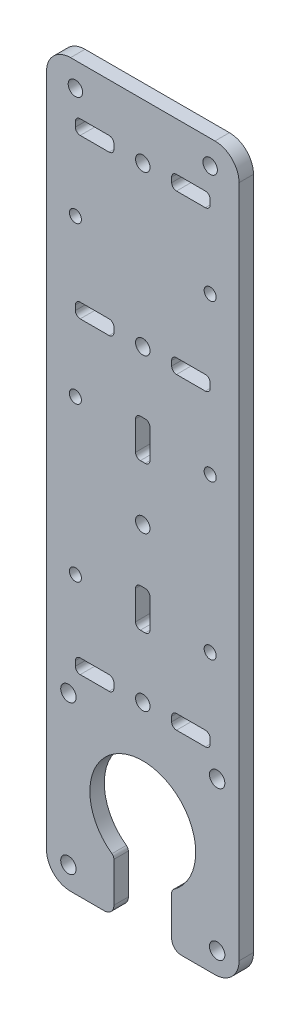
SolidWorks part; units mm, degrees
material "Acrylic (Medium-high impact)"
ref_plane "Front Plane" through (0, 0, 0) normal (0, 0, 1) x (1, 0, 0)
ref_plane "Top Plane" through (0, 0, 0) normal (0, 1, 0) x (1, 0, 0)
ref_plane "Right Plane" through (0, 0, 0) normal (1, 0, 0) x (0, 0, -1)
sketch "Sketch1" plane through (0, 0, 0) normal (0, 0, 1) x (1, 0, 0)
  line L0 (0, 75) -> (0, -75) construction
  line L1 (-20, 75) -> (20, 75)
  line L2 (-20, 75) -> (-20, -75)
  line L3 (-20, -75) -> (20, -75)
  line L4 (20, 75) -> (20, -75)
  line L5 (20, 0) -> (-20, 0) construction
  line L6 (0, -75) -> (0, -55) construction
  line L7 (0, -55) -> (6, -55) construction
  line L8 (6, -55) -> (6, -75) construction
  line L9 (0, -55) -> (-6, -55) construction
  line L10 (-6, -55) -> (-6, -75) construction
  line L11 (0, -55) -> (20, -75) construction
  line L12 (0, -55) -> (15.4503, -70.4503) construction
  line L13 (-6, -75) -> (-6, -64.2195)
  line L14 (6, -75) -> (6, -64.2195)
  line L15 (0, -75) -> (0, -35) construction
  line L16 (-20, -35) -> (20, -35) construction
  line L17 (0, -35) -> (0, -32) construction
  line L18 (-20, -32) -> (20, -32) construction
  circle A0 centre (0, -55) radius 11
  circle A1 centre (15.4503, -70.4503) radius 1.6
  circle A2 centre (-15.4503, -70.4503) radius 1.6
  circle A3 centre (-15.4503, -39.5497) radius 1.6
  circle A4 centre (15.4503, -39.5497) radius 1.6
  point P8 (0, 0)
  point P26 (0, -55)
  dimension "D1" = 4
extrude "Boss-Extrude1" add sketch "Sketch1" along normal blind 3 contours A0 L14 L3 L4 L1 L2 L13 A4 A3 A2 A1 region at (0, 5.617, 0)
fillet "Fillet1" radius 5 4 edges at (-20, -75, 1.5) (20, -75, 1.5) (-20, 75, 1.5) (20, 75, 1.5)
fillet "Fillet2" radius 2 2 edges at (6, -75, 1.5) (-6, -75, 1.5)
fillet "Fillet3" radius 1 2 edges at (6, -64.2195, 1.5) (-6, -64.2195, 1.5)
sketch "Sketch2" plane through (0, 0, 3) normal (0, 0, 1) x (1, 0, 0)
  line L0 (0, -75) -> (0, -35) construction
  line L1 (0, -35) -> (0, -33.5) construction
  line L2 (-20, -33.5) -> (20, -33.5) construction
  line L3 (-20, 70) -> (-20, -70) construction
  line L4 (20, 70) -> (20, -70) construction
  line L5 (-20, -35) -> (20, -35) construction
  line L6 (20, -35) -> (20, -32)
  line L7 (20, -32) -> (-20, -32) construction
  line L8 (-20, -32) -> (-20, -35)
  line L9 (0, 75) -> (0, 65) construction
  line L10 (-15, 75) -> (15, 75) construction
  line L11 (0, 65) -> (0, 62) construction
  line L12 (0, 62) -> (0, 32) construction
  line L13 (0, 32) -> (0, 29) construction
  line L14 (-20, 29) -> (20, 29) construction
  line L15 (20, 29) -> (20, 32) construction
  line L16 (20, 32) -> (-20, 32) construction
  line L17 (-20, 32) -> (-20, 29) construction
  line L18 (-20, 62) -> (20, 62) construction
  line L19 (20, 62) -> (20, 65) construction
  line L20 (-10, 65) -> (-10, -35) construction
  line L21 (-20, 65) -> (-20, 62) construction
  line L22 (-20, 65) -> (0, 65) construction
  line L23 (0, 65) -> (20, 65) construction
  line L24 (10, 65) -> (10, -35) construction
  line L25 (0, -33.5) -> (0, 30.5) construction
  line L26 (-10, 65) -> (-6, 65) construction
  line L27 (-10, 65) -> (-14, 65) construction
  line L28 (10, 65) -> (14, 65) construction
  line L29 (10, 65) -> (6, 65) construction
  line L30 (6, 65) -> (6, -35) construction
  line L31 (14, 65) -> (14, -35) construction
  line L32 (-14, 65) -> (-14, -35) construction
  line L33 (-6, 65) -> (-6, -35) construction
  line L34 (0, 29) -> (0, -32) construction
  line L35 (-14, 65) -> (-6, 65)
  line L36 (-14, 65) -> (-14, 62)
  line L37 (-14, 62) -> (-6, 62)
  line L38 (-6, 65) -> (-6, 62)
  line L39 (6, 65) -> (14, 65)
  line L40 (6, 65) -> (6, 62)
  line L41 (6, 62) -> (14, 62)
  line L42 (14, 65) -> (14, 62)
  line L43 (-14, 32) -> (-6, 32)
  line L44 (-14, 32) -> (-14, 29)
  line L45 (-14, 29) -> (-6, 29)
  line L46 (-6, 32) -> (-6, 29)
  line L47 (6, 32) -> (14, 32)
  line L48 (6, 32) -> (6, 29)
  line L49 (6, 29) -> (14, 29)
  line L50 (14, 32) -> (14, 29)
  line L51 (-14, -32) -> (-6, -32)
  line L52 (-14, -32) -> (-14, -35)
  line L53 (-14, -35) -> (-6, -35)
  line L54 (-6, -32) -> (-6, -35)
  line L55 (6, -32) -> (14, -32)
  line L56 (6, -32) -> (6, -35)
  line L57 (6, -35) -> (14, -35)
  line L58 (14, -32) -> (14, -35)
  circle A0 centre (0, -33.5) radius 1.5
  circle A1 centre (0, 30.5) radius 1.5
  circle A2 centre (0, 63.5) radius 1.5
  circle A3 centre (0, -1.5) radius 1.5
extrude "Cut-Extrude1" cut sketch "Sketch2" against normal blind 3 contours L54 L51 L52 L53 | L58 L55 L56 L57 | A0 | A1 | L50 L47 L48 L49 | L46 L43 L44 L45 | A2 | L38 L35 L36 L37 | L42 L39 L40 L41 | A3 region at (-10, 63.5, 3) region at (10, 63.5, 3) region at (-10, 30.5, 3) region at (10, 30.5, 3) region at (-10, -33.5, 3) region at (10, -33.5, 3) region at (0, -33.5, 3) region at (0, 30.5, 3) region at (0, 63.5, 3) region at (0, -1.5, 3)
fillet "Fillet4" radius 1 24 edges at (-6, 29, 1.5) (-14, 29, 1.5) (-6, 32, 1.5) (14, -35, 1.5) (6, -35, 1.5) (6, -32, 1.5) (14, -32, 1.5) (-6, -35, 1.5) (-14, -35, 1.5) (-14, -32, 1.5) (-6, -32, 1.5) (14, 29, 1.5) (6, 29, 1.5) (6, 32, 1.5) (14, 32, 1.5) (-14, 32, 1.5) (14, 65, 1.5) (14, 62, 1.5) (6, 65, 1.5) (6, 62, 1.5) (-14, 62, 1.5) (-6, 62, 1.5) (-6, 65, 1.5) (-14, 65, 1.5)
sketch "Sketch3" plane through (0, 0, 3) normal (0, 0, 1) x (1, 0, 0)
  line L0 (-14, 30.5) -> (-14, -1.5) construction
  line L1 (14, -1.5) -> (14, 30.5) construction
  line L2 (14, 31) -> (14, 30) construction
  line L3 (-14, 31) -> (-14, 30) construction
  line L4 (-14, -1.5) -> (-14, -33.5) construction
  line L5 (-14, -33) -> (-14, -34) construction
  line L6 (-14, -1.5) -> (14, -1.5) construction
  line L7 (14, -1.5) -> (14, -33.5) construction
  line L8 (14, -33) -> (14, -34) construction
  line L9 (-14, 30.5) -> (-14, 63.5) construction
  line L10 (-14, 64) -> (-14, 63) construction
  line L11 (14, 63.5) -> (14, 30.5) construction
  line L12 (14, 64) -> (14, 63) construction
  point P18 (-14, 47)
  point P21 (14, 47)
  point P22 (14, 14.5)
  point P23 (-14, 14.5)
  point P24 (-14, -17.5)
  point P25 (14, -17.5)
hole_wizard "Ø2.5 (2.5) Diameter Hole1" positions "Sketch7" profile "Sketch6" hole size "Ø2.5" standard "ISO"
sketch "Sketch7" plane through (0, 0, 3) normal (0, 0, 1) x (1, 0, 0)
  point P0 (14, -17.5)
  point P3 (-14, -17.5)
  point P6 (-14, 14.5)
  point P9 (14, 14.5)
  point P12 (14, 47)
  point P15 (-14, 47)
sketch "Sketch6" plane through (14, -17.5, 3) normal (1, 0, 0) x (0, -1, 0)
  line L0 (0, 0) -> (0, 6.7511)
  line L1 (0, 6.7511) -> (1.25, 6)
  line L2 (1.25, 6) -> (1.25, 0)
  line L5 (1.25, 0) -> (0, 0)
  line L10 (0, 6.7511) -> (-1.25, 6) construction
  line L11 (0, -6.35) -> (0, 107.95) construction
  dimension "Hole Dia." = 2.5
  dimension "Hole Depth" = 6
  dimension "Drill Angle" = 118
sketch "Sketch8" plane through (0, 0, 3) normal (0, 0, 1) x (1, 0, 0)
  line L0 (0, 75) -> (0, 70) construction
  line L1 (-15, 75) -> (15, 75) construction
  line L2 (0, 70) -> (-20, 70) construction
  line L3 (0, 70) -> (20, 70) construction
  line L4 (20, 70) -> (14, 70) construction
  line L5 (-20, 70) -> (-14, 70) construction
  circle A0 centre (-14, 70) radius 1.5
  circle A1 centre (14, 70) radius 1.5
extrude "Cut-Extrude2" cut sketch "Sketch8" against normal blind 10
sketch "Sketch9" plane through (0, 0, 3) normal (0, 0, 1) x (1, 0, 0)
  line L0 (0, 13.75) -> (1.5, 13.75) construction
  line L1 (-14, -1.5) -> (14, -1.5) construction
  line L2 (-14, -1.5) -> (14, -1.5) construction
  line L3 (1.5, 13.75) -> (1.5, 9.75) construction
  line L4 (1.5, 9.75) -> (-1.5, 9.75) construction
  line L5 (-1.5, 9.75) -> (-1.5, 17.75) construction
  line L6 (-1.5, 17.75) -> (1.5, 17.75) construction
  line L7 (-1.5, -12.75) -> (1.5, -12.75)
  line L8 (1.5, 17.75) -> (1.5, 13.75) construction
  line L9 (-1.5, 17.75) -> (1.5, 17.75)
  line L10 (-1.5, 17.75) -> (-1.5, 9.75)
  line L11 (-1.5, 9.75) -> (1.5, 9.75)
  line L12 (1.5, 17.75) -> (1.5, 9.75)
  line L13 (1.5, -20.75) -> (1.5, -12.75)
  line L14 (-1.5, -20.75) -> (1.5, -20.75)
  line L15 (0, -1.5) -> (0, 29) construction
  line L16 (-1.5, -20.75) -> (-1.5, -12.75)
  circle A1 centre (0, 30.5) radius 1.5 construction
extrude "Cut-Extrude3" cut sketch "Sketch9" against normal blind 10
fillet "Fillet7" radius 1 8 edges at (-1.5, 9.75, 1.5) (-1.5, 17.75, 1.5) (1.5, 17.75, 1.5) (1.5, 9.75, 1.5) (1.5, -20.75, 1.5) (-1.5, -20.75, 1.5) (-1.5, -12.75, 1.5) (1.5, -12.75, 1.5)
